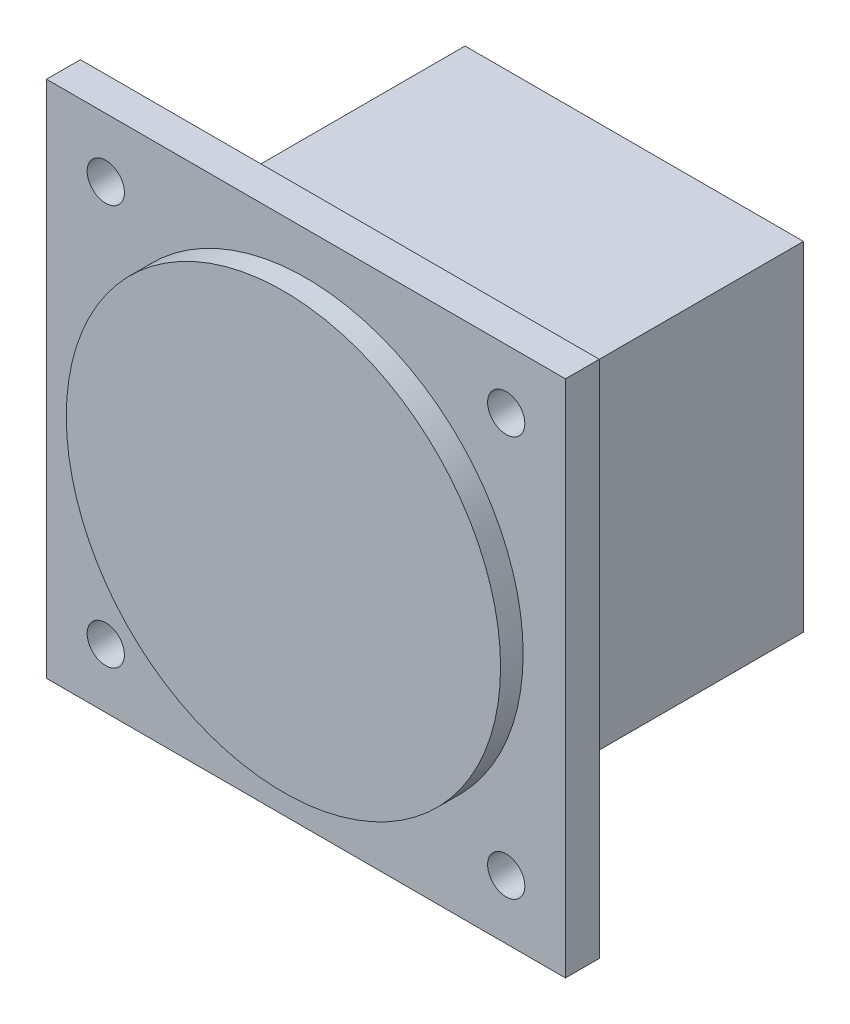
SolidWorks part; units mm, degrees
ref_plane "Front Plane" through (0, 0, 0) normal (0, 0, 1) x (1, 0, 0)
ref_plane "Top Plane" through (0, 0, 0) normal (0, 1, 0) x (1, 0, 0)
ref_plane "Right Plane" through (0, 0, 0) normal (1, 0, 0) x (0, 0, -1)
sketch "Sketch1" plane through (0, 0, 0) normal (0, 0, 1) x (1, 0, 0)
  line L5 (-23, 23) -> (23, 23)
  line L6 (-23, 23) -> (-23, -23)
  line L7 (-23, -23) -> (23, -23)
  line L8 (23, 23) -> (23, -23)
  line L9 (-23, 23) -> (23, -23) construction
  line L10 (-23, -23) -> (23, 23) construction
  circle A2 centre (0, 0) radius 20
  arc A3 (-23, -10.0504) -> (-10.0504, -23) centre (0, 0) ccw
  arc A4 (-10.0504, 23) -> (-23, 10.0504) centre (0, 0) ccw
  arc A7 (23, 10.0504) -> (10.0504, 23) centre (0, 0) ccw
  arc A8 (10.0504, -23) -> (23, -10.0504) centre (0, 0) ccw
  circle A9 centre (-17.7484, -17.7484) radius 1.65
  circle A10 centre (-17.7484, 17.7484) radius 1.65
  circle A11 centre (17.7484, 17.7484) radius 1.65
  circle A12 centre (17.7484, -17.7484) radius 1.65
  point P26 (0, 0)
  dimension "D1" = 40
  dimension "D4" = 46
  dimension "D2" = 50.2
  dimension "D5" = 3.3
  dimension "D3" = 46
  dimension "D6" = 4
extrude "Boss-Extrude1" add sketch "Sketch1" along normal blind 3 contours A12 A8 L8 A7 A11 L5 A4 A10 L6 A3 A9 L7 A2 | A2 | A11 A7 L8 L5 | A10 A4 L5 L6 | A12 A8 L7 L8 | A9 A3 L6 L7 region at (-19.3257, 19.3257, 0) region at (0, 22.3495, 0) region at (19.3257, 19.3257, 0) region at (-19.3257, -19.3257, 0) region at (19.3257, -19.3257, 0) region at (0, 0, 0)
sketch "Sketch2" plane through (0, 0, 3) normal (0, 0, 1) x (1, 0, 0)
  line L0 (0, 23) -> (0, -23) construction
  line L1 (-23, 23) -> (23, 23) construction
  line L2 (-23, -23) -> (23, -23) construction
  line L3 (-23, 0) -> (23, 0) construction
  line L4 (-23, 23) -> (-23, -23) construction
  line L5 (23, 23) -> (23, -23) construction
  circle A0 centre (0, 0) radius 19.25
  dimension "D1" = 38.5
extrude "Boss-Extrude2" add sketch "Sketch2" along normal blind 2
sketch "Sketch3" plane through (0, 0, 0) normal (0, 0, -1) x (-1, 0, 0)
  line L1 (-15, 15) -> (15, 15)
  line L2 (-15, 15) -> (-15, -15)
  line L3 (-15, -15) -> (15, -15)
  line L4 (15, 15) -> (15, -15)
  line L5 (-15, 15) -> (15, -15) construction
  line L6 (-15, -15) -> (15, 15) construction
  point P0 (0, 0)
  dimension "D1" = 30
  dimension "D2" = 30
extrude "Boss-Extrude3" add sketch "Sketch3" along normal blind 26.1
